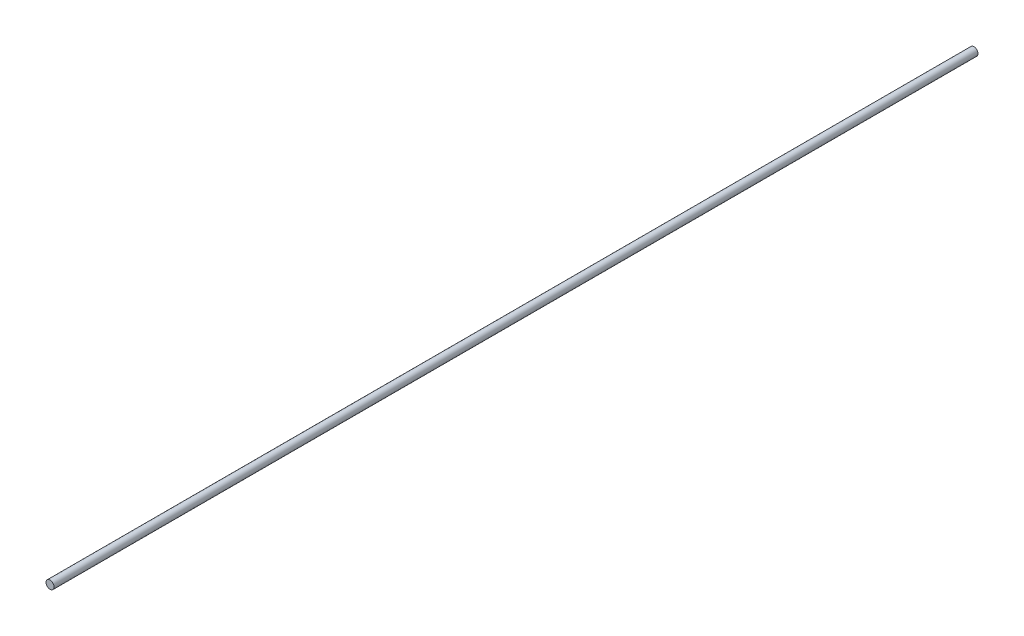
SolidWorks part; units mm, degrees
material "AISI 1020"
ref_plane "Front Plane" through (0, 0, 0) normal (0, 0, 1) x (1, 0, 0)
ref_plane "Top Plane" through (0, 0, 0) normal (0, 1, 0) x (1, 0, 0)
ref_plane "Right Plane" through (0, 0, 0) normal (1, 0, 0) x (0, 0, -1)
sketch "Sketch1" plane through (0, 0, 0) normal (0, 0, 1) x (1, 0, 0)
  circle A0 centre (0, 0) radius 7.9375
  dimension "D1" = 15.875
extrude "Boss-Extrude1" add sketch "Sketch1" along normal blind 2254.25
sketch "Sketch2" plane through (0, 0, 0) normal (0, 0, -1) x (-1, 0, 0)
  circle A0 centre (0, 0) radius 7.9375
extrude "Cut-Extrude1" cut sketch "Sketch2" against normal blind 438.15
